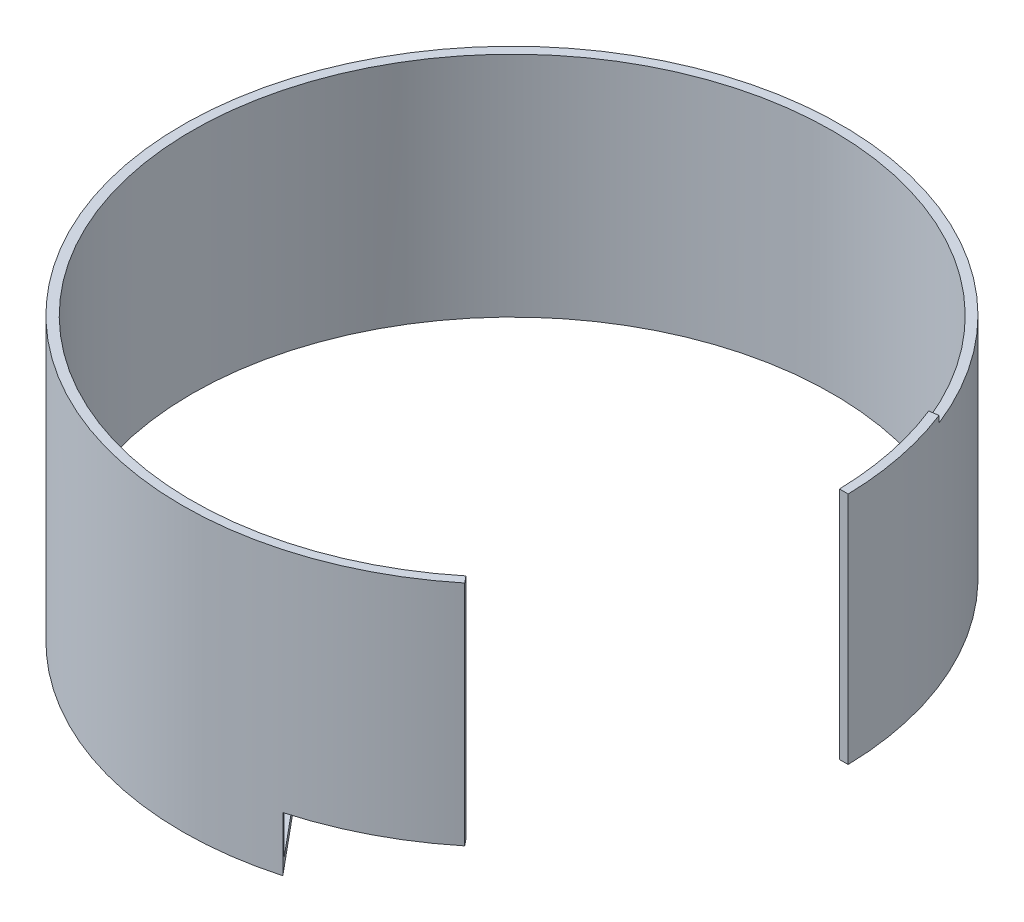
SolidWorks part; units mm, degrees
note: The reader was unsure of these and kept them because the rebuilt part matched: thickness of "Base-Flange1", "Sheet-Metal1", "Sheet-Metal4", "Sheet-Metal5", "Sheet-Metal6", "Sheet-Metal7".
material "6061-T6 (SS)"
ref_plane "X-Y Datum" through (0, 0, 0) normal (0, 0, 1) x (1, 0, 0)
ref_plane "X-Z Datum" through (0, 0, 0) normal (0, 1, 0) x (1, 0, 0)
ref_plane "Y-Z Datum" through (0, 0, 0) normal (1, 0, 0) x (0, 0, -1)
sketch "Sketch3" plane through (0, 0, 0) normal (0, 1, 0) x (1, 0, 0)
  line L0 (116.6473, 2.54) -> (119.8223, 2.54)
  line L1 (73.6453, -90.4955) -> (75.6519, -92.956)
  circle A0 centre (0, 0) radius 113.5 construction
  circle A1 centre (0, 0) radius 116.675 construction
  arc A3 (116.6473, 2.54) -> (73.6453, -90.4955) centre (0, 0) ccw
  arc A5 (119.8223, 2.54) -> (75.6519, -92.956) centre (-0.1847, 0.0845) ccw
  dimension "D1" = 227
  dimension "D3" = 3.175
  dimension "D6" = 3.175
  dimension "D4" = 2.54
  dimension "D5" = 73.6453
  dimension "D2" = 3.175
base flange "Base-Flange1" sketch "Sketch3" thickness 98.298 reverse thickness direction no parameters "D1"=0.7366
sketch "Sketch11" plane through (0, -98.298, 0) normal (0, -1, 0) x (1, 0, 0)
  line L2 (32.0004, 115.5521) -> (29.7302, 112.8236)
  line L3 (73.6453, 90.4955) -> (75.6519, 92.956)
  line L4 (-89.6892, 74.6251) -> (-37.9034, 31.5372)
  line L5 (-92.3373, 76.8285) -> (-89.6892, 74.6251)
  line L6 (116.6473, -2.54) -> (119.8223, -2.54)
  line L7 (-37.9034, 31.5372) -> (29.7302, 112.8236)
  line L8 (-7.4701, 76.9747) -> (13.6997, 102.4179) construction
  arc A0 (32.0004, 115.5521) -> (75.6519, 92.956) centre (-0.1847, -0.0845) cw
  arc A1 (75.6519, 92.956) -> (119.8223, -2.54) centre (-0.1847, -0.0845) ccw construction
  arc A2 (-92.3373, 76.8285) -> (32.0004, 115.5521) centre (-0.1847, -0.0845) cw
  arc A3 (73.6453, 90.4955) -> (116.6473, -2.54) centre (0, 0) ccw construction
  arc A4 (29.7302, 112.8236) -> (73.6453, 90.4955) centre (0, 0) cw
  arc A5 (-89.6892, 74.6251) -> (116.6473, -2.54) centre (0, 0) ccw
  arc A6 (-92.3373, 76.8285) -> (119.8223, -2.54) centre (-0.1847, -0.0845) ccw
  circle A7 centre (-7.4701, 76.9747) radius 3.5
  circle A8 centre (13.6997, 102.4179) radius 3.5
  dimension "D4" = 7
  dimension "D1" = 67.3671
  dimension "D2" = 54.3933
  dimension "D3" = 5.6673
  dimension "D5" = 33.0986
  dimension "D6" = 37.7187
  dimension "D7" = 105.744
extrude "Cut-Extrude1" cut sketch "Sketch11" against normal blind 19.939 contours A6 L6 A5 L5 | L2 A4 L3 A0 normal cut yes
sketch "Sketch13" plane through (0, -98.298, 0) normal (0, -1, 0) x (1, 0, 0)
  line L4 (-53.9503, 61.0013) -> (-21.5511, 99.9407)
  line L8 (-37.9034, 31.5372) -> (29.7302, 112.8236) construction
  line L9 (-89.6892, 74.6251) -> (-37.9034, 31.5372) construction
  line L10 (-44.1877, 52.8784) -> (-11.7885, 91.8178)
  line L11 (-37.9034, 31.5372) -> (29.7302, 112.8236)
  line L12 (-89.6892, 74.6251) -> (-37.9034, 31.5372)
  line L13 (-71.0244, 77.5194) -> (-51.2036, 100.9022)
  line L14 (-61.3366, 69.3074) -> (-41.5158, 92.6902)
  arc A0 (29.7302, 112.8236) -> (-89.6892, 74.6251) centre (0, 0) ccw construction
  arc A1 (29.7302, 112.8236) -> (-89.6892, 74.6251) centre (0, 0) ccw
  circle A2 centre (-66.1805, 73.4134) radius 6.35 construction
  circle A4 centre (-46.3597, 96.7962) radius 6.35 construction
  circle A8 centre (-10.6211, 78.2262) radius 3.5
  circle A9 centre (10.3934, 103.4828) radius 3.5
  circle A10 centre (-49.069, 56.9398) radius 6.35 construction
  circle A11 centre (-16.6698, 95.8792) radius 6.35 construction
  arc A12 (-71.0244, 77.5194) -> (-61.3366, 69.3074) centre (-66.1805, 73.4134) ccw
  arc A13 (-51.2036, 100.9022) -> (-41.5158, 92.6902) centre (-46.3597, 96.7962) cw
  arc A14 (-53.9503, 61.0013) -> (-44.1877, 52.8784) centre (-49.069, 56.9398) ccw
  arc A15 (-21.5511, 99.9407) -> (-11.7885, 91.8178) centre (-16.6698, 95.8792) cw
  dimension "D4" = 86.1958
  dimension "D5" = 12.7
  dimension "D6" = 7
  dimension "D1" = 8.89
  dimension "D2" = 53.34
  dimension "D3" = 8.89
extrude "Boss-Extrude3" add sketch "Sketch13" against normal blind 3.175
sketch "Sketch14" plane through (0, 0, 0) normal (0, 1, 0) x (1, 0, 0)
  line L2 (116.6473, 2.54) -> (119.8223, 2.54)
  line L3 (75.6519, -92.956) -> (73.6453, -90.4955)
  line L4 (116.6473, 2.54) -> (119.8223, 2.54)
  line L5 (75.6519, -92.956) -> (73.6453, -90.4955)
  arc A2 (116.6473, 2.54) -> (73.6453, -90.4955) centre (0, 0) ccw
  arc A3 (119.8223, 2.54) -> (75.6519, -92.956) centre (-0.1847, 0.0845) ccw
  arc A4 (116.6473, 2.54) -> (73.6453, -90.4955) centre (0, 0) ccw
  arc A5 (119.8223, 2.54) -> (75.6519, -92.956) centre (-0.1847, 0.0845) ccw
  dimension "D1" = 0
extrude "Boss-Extrude4" add sketch "Sketch14" along normal blind 4.572 contours A4 L5 A5 L4
sketch "Sketch15" plane through (0, 4.572, 0) normal (0, 1, 0) x (1, 0, 0)
  line L0 (116.6473, 2.54) -> (119.8223, 2.54) construction
  line L1 (116.6473, 2.54) -> (119.8223, 2.54)
  line L2 (108.3049, 43.3947) -> (111.5699, 43.8866)
  arc A0 (116.6473, 2.54) -> (73.6453, -90.4955) centre (0, 0) ccw construction
  arc A1 (119.8223, 2.54) -> (75.6519, -92.956) centre (-0.1847, 0.0845) ccw construction
  arc A2 (116.6473, 2.54) -> (73.6453, -90.4955) centre (0, 0) ccw construction
  arc A3 (119.8223, 2.54) -> (75.6519, -92.956) centre (-0.1847, 0.0845) ccw construction
  arc A4 (116.6473, 2.54) -> (108.3049, 43.3947) centre (0, 0) ccw
  arc A5 (119.8223, 2.54) -> (111.5699, 43.8866) centre (-0.1847, 0.0845) ccw
  dimension "D2" = 3.265
extrude "Boss-Extrude5" add sketch "Sketch15" along normal blind 2.4115
sketch "Bend-Lines1" [suppressed] plane through (0, 0, 0) normal (0, 1, 0) x (1, 0, 0)
sketch "Bounding-Box1" [suppressed] plane through (0, 0, 0) normal (0, 1, 0) x (1, 0, 0)
sheet metal parameters "Sheet-Metal1" thickness 98.298 parameters "D1"=0.7366
flat pattern "Flat-Pattern1" [suppressed]
sketch "Bend-Lines2" plane through (0, 0, 0) normal (0, 1, 0) x (1, 0, 0)
sketch3d "Bounding-Box2" [suppressed]
  line L0 (148.6796, 65.5145, 0) -> (52.1341, -153.8825, 0) construction
  line L1 (-61.4257, 157.9712, 0) -> (-157.9712, -61.4257, 0) construction
  line L2 (148.6796, 65.5145, 0) -> (-61.4257, 157.9712, 0) construction
  line L3 (52.1341, -153.8825, 0) -> (-157.9712, -61.4257, 0) construction
sketch "Sketch11-1" [suppressed] plane through (0, -97, 0) normal (0, -1, 0) x (1, 0, 0)
  line L0 (-91.6809, 77.1922) -> (-40.3111, 33.9406)
  line L1 (-40.3111, 33.9406) -> (29.0191, 116.2838)
  arc A2 (-91.6809, 77.1922) -> (29.0191, 116.2838) centre (0, 0) cw
  dimension "D1" = 40.3111
  dimension "D2" = 52.6967
  dimension "D3" = 116.2838
sheet metal parameters "Sheet-Metal4" thickness 98.298 parameters "D1"=0.7366, "D7"=86
flat pattern "Flat-Pattern1" [suppressed]
sketch "Bend-Lines2" plane through (0, 0, 0) normal (0, 1, 0) x (1, 0, 0)
sketch3d "Bounding-Box2" [suppressed]
  line L0 (-119.85, -119.85, 0) -> (119.85, -119.85, 0) construction
  line L1 (-119.85, 119.85, 0) -> (119.85, 119.85, 0) construction
  line L2 (-119.85, -119.85, 0) -> (-119.85, 119.85, 0) construction
  line L3 (119.85, -119.85, 0) -> (119.85, 119.85, 0) construction
sketch "Sketch11-1" [suppressed] plane through (0, -97, 0) normal (0, -1, 0) x (1, 0, 0)
  line L0 (-91.6809, 77.1922) -> (-40.3111, 33.9406)
  line L1 (-40.3111, 33.9406) -> (29.0191, 116.2838)
  line L2 (29.0191, 116.2838) -> (26.7348, 113.5707)
  line L3 (78.8189, 86.027) -> (80.9637, 88.368)
  line L5 (-91.6809, 77.1922) -> (-89.2521, 75.1473)
  line L6 (116.675, 0) -> (119.85, 0)
  arc A0 (29.0191, 116.2838) -> (80.9637, 88.368) centre (0, 0) cw
  arc A2 (-91.6809, 77.1922) -> (29.0191, 116.2838) centre (0, 0) cw
  arc A4 (26.7348, 113.5707) -> (78.8189, 86.027) centre (0, 0) cw
  arc A5 (-89.2521, 75.1473) -> (116.675, 0) centre (0, 0) ccw
  arc A6 (-91.6809, 77.1922) -> (119.85, 0) centre (0, 0) ccw
  dimension "D1" = 40.3111
  dimension "D2" = 52.6967
  dimension "D3" = 116.2838
sheet metal parameters "Sheet-Metal5" thickness 98.298 parameters "D1"=0.7366, "D7"=86
flat pattern "Flat-Pattern1" [suppressed]
sketch "Bend-Lines2" plane through (0, 0, 0) normal (0, 1, 0) x (1, 0, 0)
sketch3d "Bounding-Box2" [suppressed]
  line L0 (-119.85, -119.85, 0) -> (119.85, -119.85, 0) construction
  line L1 (-119.85, 119.85, 0) -> (119.85, 119.85, 0) construction
  line L2 (-119.85, -119.85, 0) -> (-119.85, 119.85, 0) construction
  line L3 (119.85, -119.85, 0) -> (119.85, 119.85, 0) construction
sketch "Sketch11-1" [suppressed] plane through (0, -86.36, 0) normal (0, -1, 0) x (1, 0, 0)
  line L2 (32.638, 115.3204) -> (30.3881, 112.6482)
  line L3 (78.8189, 86.027) -> (80.9637, 88.368)
  line L4 (-89.2521, 75.1473) -> (-37.7187, 31.7579)
  line L5 (-91.6809, 77.1922) -> (-89.2521, 75.1473)
  line L6 (116.675, 0) -> (119.85, 0)
  line L7 (-37.7187, 31.7579) -> (30.3881, 112.6482)
  line L8 (-7.0207, 77.017) -> (14.2972, 102.3362) construction
  arc A0 (32.638, 115.3204) -> (80.9637, 88.368) centre (0, 0) cw
  arc A2 (-91.6809, 77.1922) -> (32.638, 115.3204) centre (0, 0) cw
  arc A4 (30.3881, 112.6482) -> (78.8189, 86.027) centre (0, 0) cw
  arc A5 (-89.2521, 75.1473) -> (116.675, 0) centre (0, 0) ccw
  arc A6 (-91.6809, 77.1922) -> (119.85, 0) centre (0, 0) ccw
  circle A7 centre (-7.0207, 77.017) radius 3.5
  circle A8 centre (14.2972, 102.3362) radius 3.5
  dimension "D4" = 7
  dimension "D1" = 67.3671
  dimension "D2" = 54.3933
  dimension "D3" = 5.6673
  dimension "D5" = 33.0986
  dimension "D6" = 37.7187
  dimension "D7" = 105.744
sheet metal parameters "Sheet-Metal6" thickness 98.298 parameters "D1"=0.7366, "D7"=86
flat pattern "Flat-Pattern1"
sketch "Bend-Lines2" plane through (0, 0, 0) normal (0, 1, 0) x (1, 0, 0)
sketch3d "Bounding-Box2" [suppressed]
  line L0 (92.3373, -76.8285, 0) -> (22.4335, -160.8434, 0) construction
  line L1 (37.9034, -31.5372, 0) -> (-32.0004, -115.5521, 0) construction
  line L2 (92.3373, -76.8285, 0) -> (37.9034, -31.5372, 0) construction
  line L3 (22.4335, -160.8434, 0) -> (-32.0004, -115.5521, 0) construction
sheet metal parameters "Sheet-Metal7" thickness 98.298 parameters "D1"=0.7366, "D7"=86
flat pattern "Flat-Pattern1"
sketch "Bend-Lines2" plane through (0, 0, 0) normal (0, 1, 0) x (1, 0, 0)
sketch3d "Bounding-Box2" [suppressed]
  line L0 (92.3373, -76.8285, 0) -> (22.4335, -160.8434, 0) construction
  line L1 (37.9034, -31.5372, 0) -> (-32.0004, -115.5521, 0) construction
  line L2 (92.3373, -76.8285, 0) -> (37.9034, -31.5372, 0) construction
  line L3 (22.4335, -160.8434, 0) -> (-32.0004, -115.5521, 0) construction
